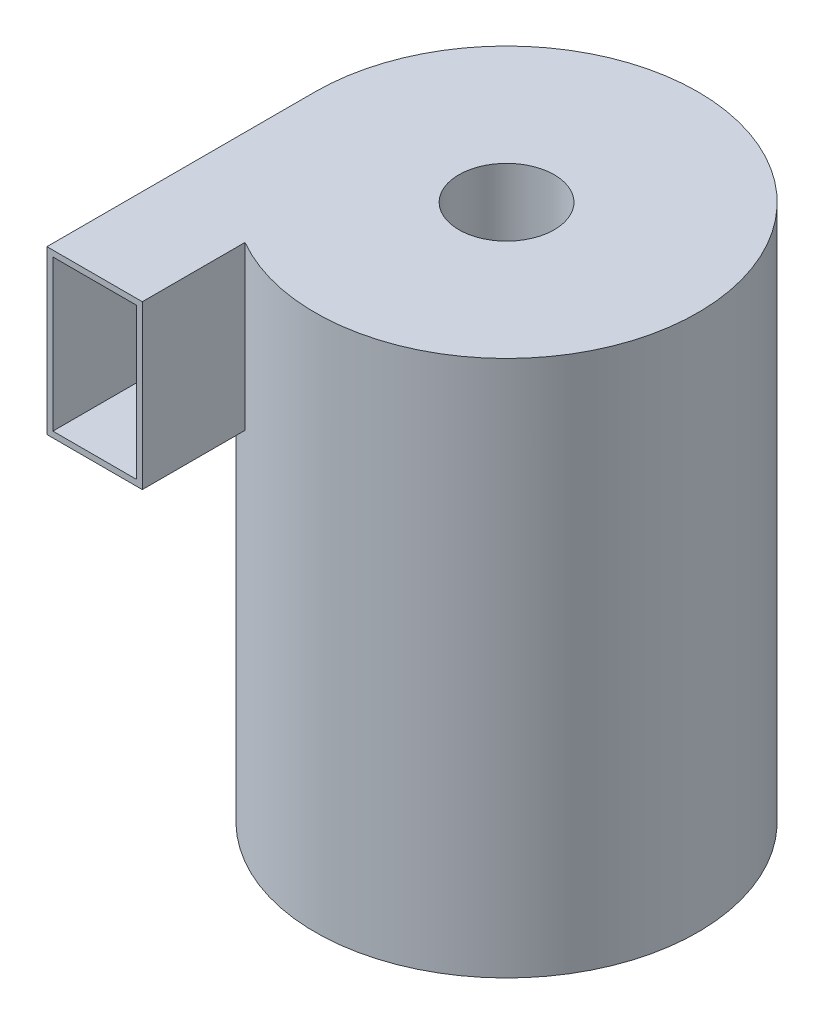
SolidWorks part; units mm, degrees
ref_plane "정면" through (0, 0, 0) normal (0, 0, 1) x (1, 0, 0)
ref_plane "윗면" through (0, 0, 0) normal (0, 1, 0) x (1, 0, 0)
ref_plane "우측면" through (0, 0, 0) normal (1, 0, 0) x (0, 0, -1)
sketch "스케치3" plane through (0, 0, 0) normal (0, 0, 1) x (1, 0, 0)
  line L0 (0, 0) -> (0, 24.4556) construction
  line L1 (0, 0) -> (17.168, 0) construction
  line L2 (0, 19) -> (8, 19)
  line L3 (8, 19) -> (8, 90)
  line L4 (8, 90) -> (32.1, 90)
  line L5 (32.1, 90) -> (32.1, 0)
  line L6 (32.1, 0) -> (0, 0)
  line L7 (0, 0) -> (0, 19)
  dimension "D1" = 32.1
  dimension "D2" = 8
  dimension "D3" = 71
  dimension "D4" = 90
revolve "회전1" add sketch "스케치3" angle 360 about L0
sketch "스케치4" plane through (0, 0, 0) normal (0, 0, 1) x (1, 0, 0)
  line L1 (-32.1, 90) -> (-16.1, 90)
  line L2 (-32.1, 90) -> (-32.1, 62.7)
  line L3 (-32.1, 62.7) -> (-16.1, 62.7)
  line L4 (-16.1, 90) -> (-16.1, 62.7)
  dimension "D1" = 27.3
  dimension "D2" = 16
extrude "보스-돌출3" add sketch "스케치4" along normal blind 45
shell "쉘2" thickness 1 removed face at (0, 0, -32.1) removed face at (-24.1, 76.35, 45) removed face at (0, 19, -8)
